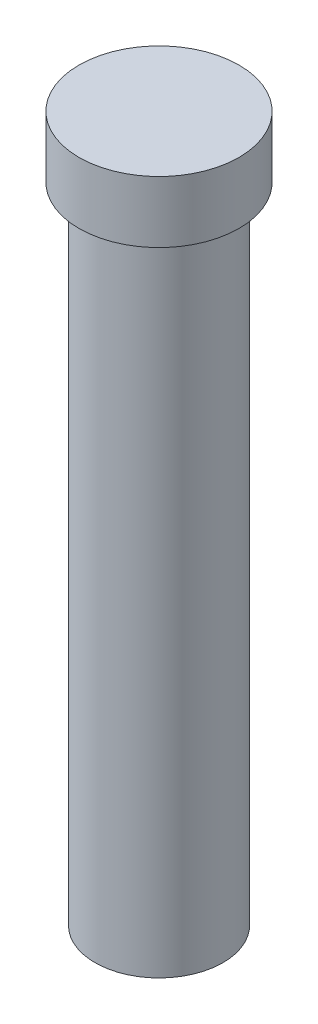
SolidWorks part; units mm, degrees
material "M2 HSS"
ref_plane "Front Plane" through (0, 0, 0) normal (0, 0, 1) x (1, 0, 0)
ref_plane "Top Plane" through (0, 0, 0) normal (0, 1, 0) x (1, 0, 0)
ref_plane "Right Plane" through (0, 0, 0) normal (1, 0, 0) x (0, 0, -1)
sketch "Sketch1" plane through (0, 0, 0) normal (0, 0, 1) x (1, 0, 0)
  line L0 (0, 0) -> (6.5, 0)
  line L1 (6.5, 0) -> (6.5, -5)
  line L2 (6.5, -5) -> (5.2, -5)
  line L3 (5.2, -5) -> (5.2, -57.3)
  line L4 (5.2, -57.3) -> (0, -57.3)
  line L5 (0, -57.3) -> (0, 0)
  line L6 (0, -62.3) -> (0, 5) construction
  dimension "D1" = 5
  dimension "D2" = 5
  dimension "D3" = 10.4
  dimension "D4" = 13
  dimension "D5" = 5
  dimension "D6" = 57.3
revolve "Revolve1" add sketch "Sketch1" angle 360 about L6
